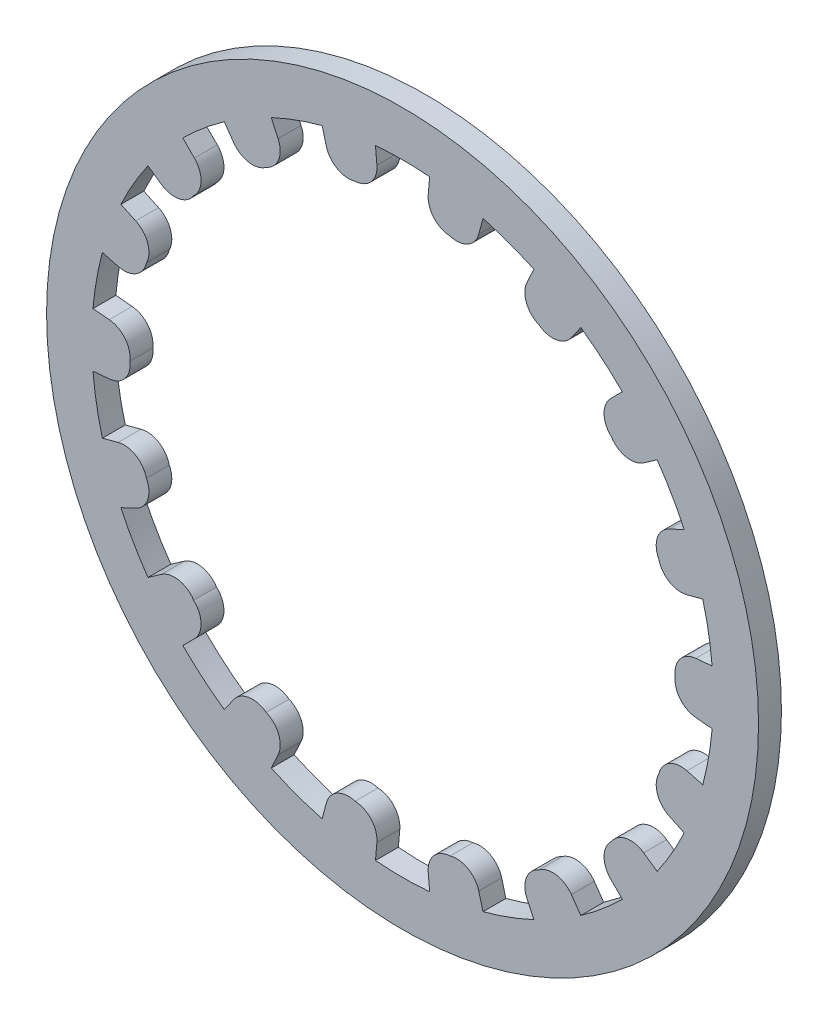
SolidWorks part; units mm, degrees
ref_plane "Front Plane" through (0, 0, 0) normal (0, 0, 1) x (1, 0, 0)
ref_plane "Top Plane" through (0, 0, 0) normal (0, 1, 0) x (1, 0, 0)
ref_plane "Right Plane" through (0, 0, 0) normal (1, 0, 0) x (0, 0, -1)
ref_plane "Plane1" through (0, 0, 0) normal (0, 0, 1) x (1, 0, 0)
sketch "Sketch1" plane through (0, 0, 0) normal (0, 0, 1) x (1, 0, 0)
  line L0 (-6.8699, 0.601) -> (-6.5086, 0.5694)
  line L1 (-6.5086, -0.5694) -> (-6.8699, -0.601)
  line L2 (-6.6611, -1.7848) -> (-6.3109, -1.691)
  line L3 (-5.9213, -2.7612) -> (-6.25, -2.9144)
  line L4 (-5.649, -3.9554) -> (-5.3519, -3.7475)
  line L5 (-4.6199, -4.6199) -> (-4.8763, -4.8763)
  line L6 (-3.9554, -5.649) -> (-3.7475, -5.3519)
  line L7 (-2.7612, -5.9213) -> (-2.9144, -6.25)
  line L8 (-1.7848, -6.6611) -> (-1.691, -6.3109)
  line L9 (-0.5694, -6.5086) -> (-0.601, -6.8699)
  line L10 (0.601, -6.8699) -> (0.5694, -6.5086)
  line L11 (1.691, -6.3109) -> (1.7848, -6.6611)
  line L12 (2.9144, -6.25) -> (2.7612, -5.9213)
  line L13 (3.7475, -5.3519) -> (3.9554, -5.649)
  line L14 (4.8763, -4.8763) -> (4.6199, -4.6199)
  line L15 (5.3519, -3.7475) -> (5.649, -3.9554)
  line L16 (6.25, -2.9144) -> (5.9213, -2.7612)
  line L17 (6.3109, -1.691) -> (6.6611, -1.7848)
  line L18 (6.8699, -0.601) -> (6.5086, -0.5694)
  line L19 (6.5086, 0.5694) -> (6.8699, 0.601)
  line L20 (6.6611, 1.7848) -> (6.3109, 1.691)
  line L21 (5.9213, 2.7612) -> (6.25, 2.9144)
  line L22 (5.649, 3.9554) -> (5.3519, 3.7475)
  line L23 (4.6199, 4.6199) -> (4.8763, 4.8763)
  line L24 (3.9554, 5.649) -> (3.7475, 5.3519)
  line L25 (2.7612, 5.9213) -> (2.9144, 6.25)
  line L26 (1.7848, 6.6611) -> (1.691, 6.3109)
  line L27 (0.5694, 6.5086) -> (0.601, 6.8699)
  line L28 (-0.601, 6.8699) -> (-0.5694, 6.5086)
  line L29 (-1.691, 6.3109) -> (-1.7848, 6.6611)
  line L30 (-2.9144, 6.25) -> (-2.7612, 5.9213)
  line L31 (-3.7475, 5.3519) -> (-3.9554, 5.649)
  line L32 (-4.8763, 4.8763) -> (-4.6199, 4.6199)
  line L33 (-5.3519, 3.7475) -> (-5.649, 3.9554)
  line L34 (-6.25, 2.9144) -> (-5.9213, 2.7612)
  line L35 (-6.3109, 1.691) -> (-6.6611, 1.7848)
  circle A0 centre (0, 0) radius 7.8994
  arc A1 (-6.5086, 0.5694) -> (-6.0489, 0) centre (-6.5529, 0.0634) cw
  arc A2 (-6.0489, 0) -> (-6.5086, -0.5694) centre (-6.5529, -0.0634) cw
  arc A3 (-6.8699, -0.601) -> (-6.6611, -1.7848) centre (0, 0) ccw
  arc A4 (-6.3109, -1.691) -> (-5.6841, -2.0688) centre (-6.1794, -2.1817) cw
  arc A5 (-5.6841, -2.0688) -> (-5.9213, -2.7612) centre (-6.136, -2.3008) cw
  arc A6 (-6.25, -2.9144) -> (-5.649, -3.9554) centre (0, 0) ccw
  arc A7 (-5.3519, -3.7475) -> (-4.6337, -3.8881) centre (-5.0605, -4.1636) cw
  arc A8 (-4.6337, -3.8881) -> (-4.6199, -4.6199) centre (-4.9791, -4.2607) cw
  arc A9 (-4.8763, -4.8763) -> (-3.9554, -5.649) centre (0, 0) ccw
  arc A10 (-3.7475, -5.3519) -> (-3.0244, -5.2385) centre (-3.3313, -5.6433) cw
  arc A11 (-3.0244, -5.2385) -> (-2.7612, -5.9213) centre (-3.2216, -5.7067) cw
  arc A12 (-2.9144, -6.25) -> (-1.7848, -6.6611) centre (0, 0) ccw
  arc A13 (-1.691, -6.3109) -> (-1.0504, -5.957) centre (-1.2003, -6.4423) cw
  arc A14 (-1.0504, -5.957) -> (-0.5694, -6.5086) centre (-1.0755, -6.4643) cw
  arc A15 (-0.601, -6.8699) -> (0.601, -6.8699) centre (0, 0) ccw
  arc A16 (0.5694, -6.5086) -> (1.0504, -5.957) centre (1.0755, -6.4643) cw
  arc A17 (1.0504, -5.957) -> (1.691, -6.3109) centre (1.2003, -6.4423) cw
  arc A18 (1.7848, -6.6611) -> (2.9144, -6.25) centre (0, 0) ccw
  arc A19 (2.7612, -5.9213) -> (3.0244, -5.2385) centre (3.2216, -5.7067) cw
  arc A20 (3.0244, -5.2385) -> (3.7475, -5.3519) centre (3.3313, -5.6433) cw
  arc A21 (3.9554, -5.649) -> (4.8763, -4.8763) centre (0, 0) ccw
  arc A22 (4.6199, -4.6199) -> (4.6337, -3.8881) centre (4.9791, -4.2607) cw
  arc A23 (4.6337, -3.8881) -> (5.3519, -3.7475) centre (5.0605, -4.1636) cw
  arc A24 (5.649, -3.9554) -> (6.25, -2.9144) centre (0, 0) ccw
  arc A25 (5.9213, -2.7612) -> (5.6841, -2.0688) centre (6.136, -2.3008) cw
  arc A26 (5.6841, -2.0688) -> (6.3109, -1.691) centre (6.1794, -2.1817) cw
  arc A27 (6.6611, -1.7848) -> (6.8699, -0.601) centre (0, 0) ccw
  arc A28 (6.5086, -0.5694) -> (6.0489, 0) centre (6.5529, -0.0634) cw
  arc A29 (6.0489, 0) -> (6.5086, 0.5694) centre (6.5529, 0.0634) cw
  arc A30 (6.8699, 0.601) -> (6.6611, 1.7848) centre (0, 0) ccw
  arc A31 (6.3109, 1.691) -> (5.6841, 2.0688) centre (6.1794, 2.1817) cw
  arc A32 (5.6841, 2.0688) -> (5.9213, 2.7612) centre (6.136, 2.3008) cw
  arc A33 (6.25, 2.9144) -> (5.649, 3.9554) centre (0, 0) ccw
  arc A34 (5.3519, 3.7475) -> (4.6337, 3.8881) centre (5.0605, 4.1636) cw
  arc A35 (4.6337, 3.8881) -> (4.6199, 4.6199) centre (4.9791, 4.2607) cw
  arc A36 (4.8763, 4.8763) -> (3.9554, 5.649) centre (0, 0) ccw
  arc A37 (3.7475, 5.3519) -> (3.0244, 5.2385) centre (3.3313, 5.6433) cw
  arc A38 (3.0244, 5.2385) -> (2.7612, 5.9213) centre (3.2216, 5.7067) cw
  arc A39 (2.9144, 6.25) -> (1.7848, 6.6611) centre (0, 0) ccw
  arc A40 (1.691, 6.3109) -> (1.0504, 5.957) centre (1.2003, 6.4423) cw
  arc A41 (1.0504, 5.957) -> (0.5694, 6.5086) centre (1.0755, 6.4643) cw
  arc A42 (0.601, 6.8699) -> (-0.601, 6.8699) centre (0, 0) ccw
  arc A43 (-0.5694, 6.5086) -> (-1.0504, 5.957) centre (-1.0755, 6.4643) cw
  arc A44 (-1.0504, 5.957) -> (-1.691, 6.3109) centre (-1.2003, 6.4423) cw
  arc A45 (-1.7848, 6.6611) -> (-2.9144, 6.25) centre (0, 0) ccw
  arc A46 (-2.7612, 5.9213) -> (-3.0244, 5.2385) centre (-3.2216, 5.7067) cw
  arc A47 (-3.0244, 5.2385) -> (-3.7475, 5.3519) centre (-3.3313, 5.6433) cw
  arc A48 (-3.9554, 5.649) -> (-4.8763, 4.8763) centre (0, 0) ccw
  arc A49 (-4.6199, 4.6199) -> (-4.6337, 3.8881) centre (-4.9791, 4.2607) cw
  arc A50 (-4.6337, 3.8881) -> (-5.3519, 3.7475) centre (-5.0605, 4.1636) cw
  arc A51 (-5.649, 3.9554) -> (-6.25, 2.9144) centre (0, 0) ccw
  arc A52 (-5.9213, 2.7612) -> (-5.6841, 2.0688) centre (-6.136, 2.3008) cw
  arc A53 (-5.6841, 2.0688) -> (-6.3109, 1.691) centre (-6.1794, 2.1817) cw
  arc A54 (-6.6611, 1.7848) -> (-6.8699, 0.601) centre (0, 0) ccw
extrude "Boss-Extrude1" add sketch "Sketch1" against normal blind 0.254 and the other way blind 0.254
